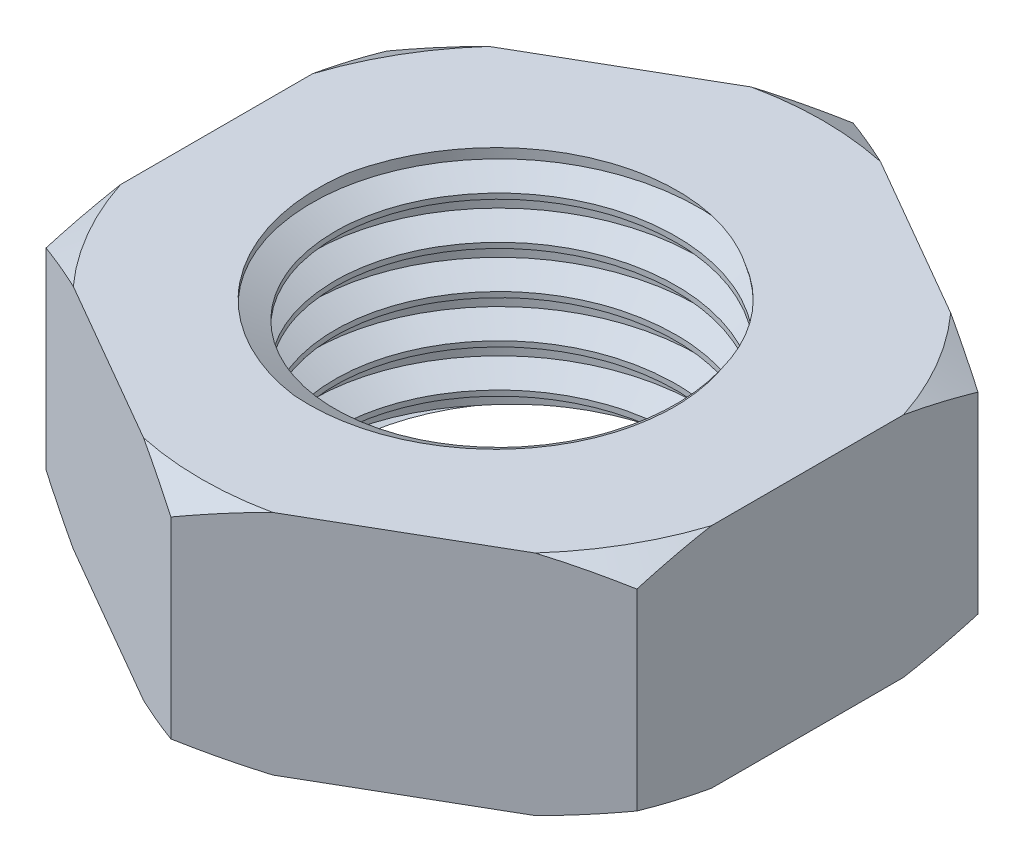
SolidWorks part; units mm, degrees
ref_plane "Front Plane" through (0, 0, 0) normal (0, 0, 1) x (1, 0, 0)
ref_plane "Top Plane" through (0, 0, 0) normal (0, 1, 0) x (1, 0, 0)
ref_plane "Right Plane" through (0, 0, 0) normal (1, 0, 0) x (0, 0, -1)
sketch "Sketch1" plane through (0, 0, 0) normal (0, 1, 0) x (1, 0, 0)
  line L1 (10.3923, 6) -> (0, 12)
  line L2 (0, 12) -> (-10.3923, 6)
  line L3 (-10.3923, 6) -> (-10.3923, -6)
  line L4 (-10.3923, -6) -> (0, -12)
  line L5 (0, -12) -> (10.3923, -6)
  line L6 (10.3923, -6) -> (10.3923, 6)
  circle A0 centre (0, 0) radius 6
  circle A1 centre (0, 0) radius 10.3923 construction
  dimension "D1" = 12
  dimension "D2" = 24
extrude "Boss-Extrude1" add sketch "Sketch1" along normal mid plane 8
thread "Thread1" pitch 1.5 method cut profile "Thread Profile1" start angle 0, offset 2, length 27, pitch 1.5, diameter 12
ref_plane "Plane1" through (-6, 6, 0) normal (0, 0, -1) x (1, 0, 0)
sketch "Thread Profile1" plane through (-6, 6, 0) normal (0, 0, -1) x (1, 0, 0)
  line L0 (0, 0) -> (0, 1.5) construction
  line L11 (0, 0) -> (0, 1.3125)
  line L12 (0, 1.3125) -> (-0.8119, 0.8437)
  line L13 (-0.8119, 0.8437) -> (-0.8119, 0.4687)
  line L15 (-0.8119, 0.4687) -> (0, 0)
  line L17 (-0.8119, 0.6562) -> (0, 0.6562) construction
  point P2 (0, 0)
  dimension "Pitch" = 1.5
  dimension "Profile_Angle" = 60
  dimension "Profile_Land" = 0.375
  dimension "Profile_Height" = 0.8119
sketch "Sketch5" plane through (0, 0, 0) normal (1, 0, 0) x (0, 0, -1)
  line L0 (0, 0) -> (0, 4.4079) construction
  line L3 (12, 4) -> (12, -4) construction
  line L4 (12, 3.3808) -> (12, 4)
  line L5 (12, 4) -> (10.9275, 4)
  line L6 (6, 4) -> (12, 4) construction
  line L7 (10.9275, 4) -> (12, 3.3808)
  dimension "D1" = 30
revolve "Cut-Revolve4" cut sketch "Sketch5" angle 360 about L0
mirror "Mirror1" about plane through (0, 0, 0) normal (0, 1, 0) of "Cut-Revolve4"
